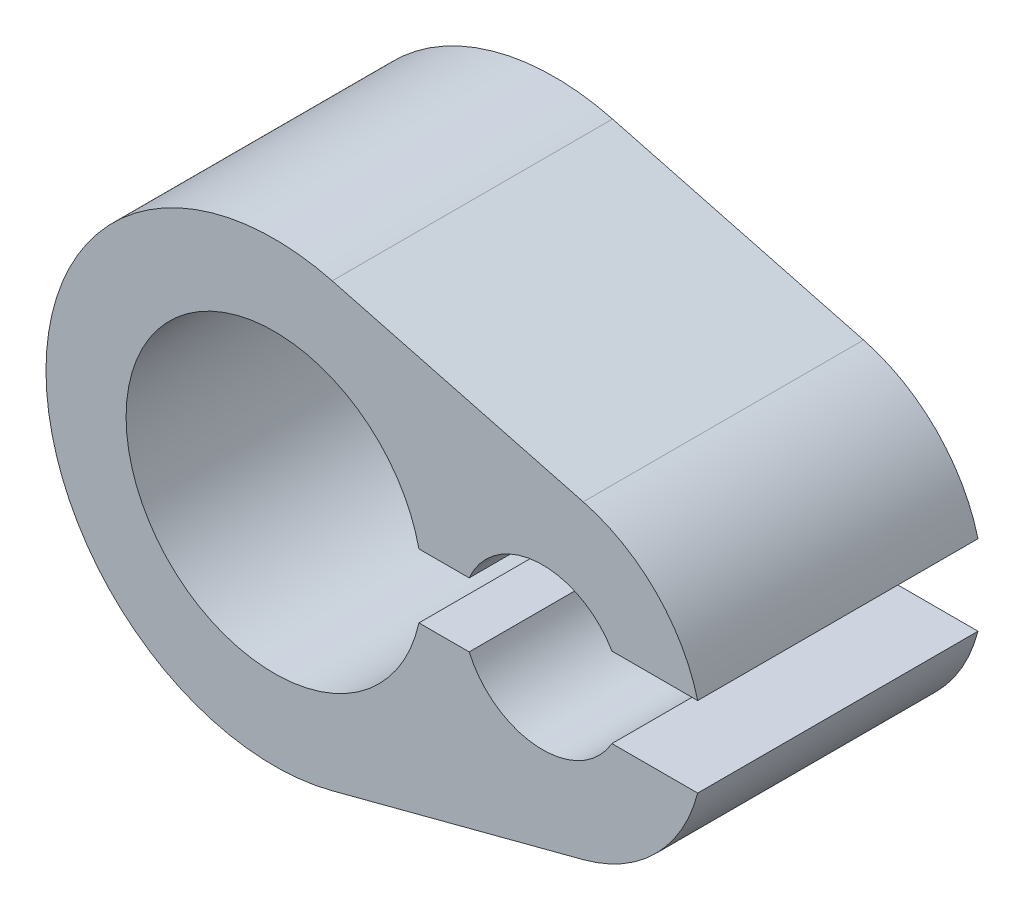
SolidWorks part; units mm, degrees
material "ABS"
ref_plane "Front Plane" through (0, 0, 0) normal (0, 0, 1) x (1, 0, 0)
ref_plane "Top Plane" through (0, 0, 0) normal (0, 1, 0) x (1, 0, 0)
ref_plane "Right Plane" through (0, 0, 0) normal (1, 0, 0) x (0, 0, -1)
sketch "Sketch1" plane through (0, 0, 0) normal (0, 0, 1) x (1, 0, 0)
  line L0 (1.4463, 5.5135) -> (7.7149, 3.8691)
  line L1 (7.7149, -3.8691) -> (1.4463, -5.5135)
  line L2 (3.6125, 0.8) -> (4.867, 0.8)
  line L3 (8.4321, 1) -> (10.573, 1)
  line L4 (3.6125, -0.8) -> (4.867, -0.8)
  line L5 (10.573, -1) -> (8.4321, -1)
  arc A0 (1.4463, 5.5135) -> (1.4463, -5.5135) centre (0, 0) ccw
  arc A1 (7.7149, -3.8691) -> (10.573, -1) centre (6.7, 0) ccw
  arc A2 (3.6125, 0.8) -> (3.6125, -0.8) centre (0, 0) ccw
  arc A3 (4.867, -0.8) -> (8.4321, -1) centre (6.7, 0) ccw
  arc A4 (8.4321, 1) -> (4.867, 0.8) centre (6.7, 0) ccw
  arc A5 (10.573, 1) -> (7.7149, 3.8691) centre (6.7, 0) ccw
  dimension "D1" = 11.4
  dimension "D2" = 8
  dimension "D3" = 6.7
  dimension "D4" = 2
  dimension "D5" = 3.7
  dimension "D6" = 1.6
  dimension "D7" = 2
extrude "Boss-Extrude1" add sketch "Sketch1" along normal blind 7
